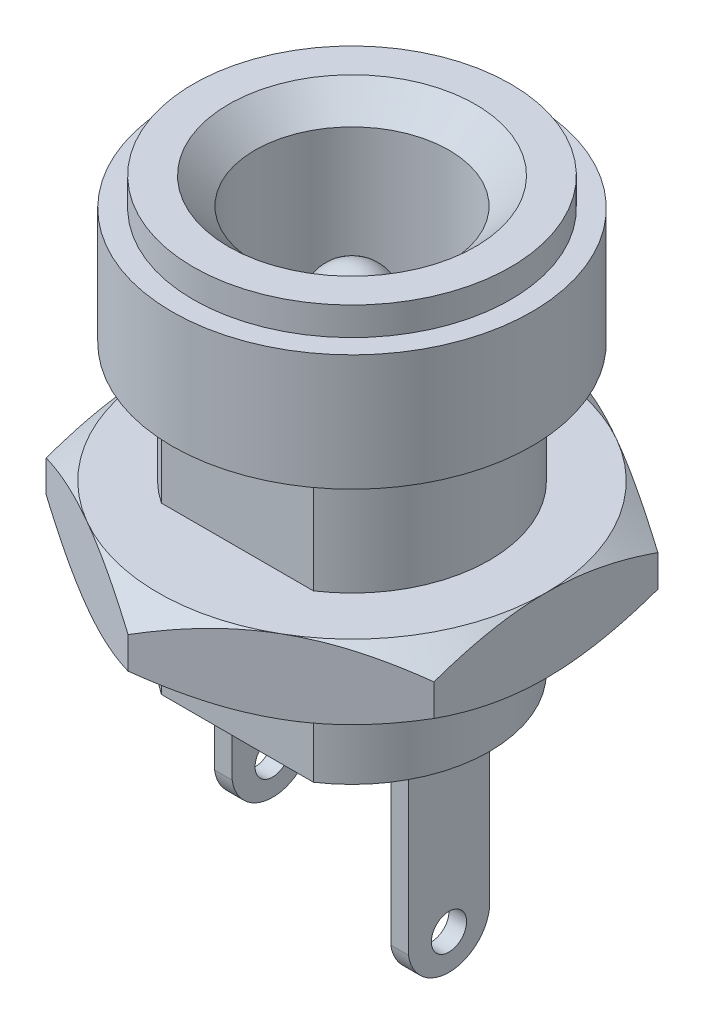
SolidWorks part; units mm, degrees
ref_plane "Front Plane" through (0, 0, 0) normal (0, 0, 1) x (1, 0, 0)
ref_plane "Top Plane" through (0, 0, 0) normal (0, 1, 0) x (1, 0, 0)
ref_plane "Right Plane" through (0, 0, 0) normal (1, 0, 0) x (0, 0, -1)
sketch "Sketch1" plane through (0, 0, 0) normal (0, 0, 1) x (1, 0, 0)
  line L0 (0, 0) -> (0, 12.2) construction
  line L1 (0, 0) -> (3.9, 0) construction
  line L2 (3.9, 0) -> (3.9, 8.1)
  line L3 (3.9, 8.1) -> (5.1, 8.1)
  line L4 (5.1, 8.1) -> (5.1, 11.4)
  line L5 (5.1, 11.4) -> (4.5, 11.4)
  line L6 (4.5, 11.4) -> (4.5, 12.2)
  line L7 (4.5, 12.2) -> (0, 12.2) construction
  line L8 (4.5, 12.2) -> (3.5, 12.2)
  line L9 (3.5, 12.2) -> (2.75, 11.45)
  line L10 (2.75, 11.45) -> (2.75, 3.2)
  line L11 (2.75, 3.2) -> (1.05, 3.2)
  line L12 (1.05, 3.2) -> (1.05, 8.95)
  line L13 (0, 2) -> (1.3, 2)
  line L14 (1.3, 2) -> (1.3, 0)
  line L15 (1.3, 0) -> (3.9, 0)
  line L16 (0, 10) -> (0, 2)
  arc A0 (1.05, 8.95) -> (0, 10) centre (0, 8.95) ccw
  dimension "D1" = 7.8
  dimension "D2" = 12.2
  dimension "D3" = 10.2
  dimension "D4" = 9
  dimension "D5" = 0.8
  dimension "D6" = 4.1
  dimension "D7" = 45
  dimension "D8" = 5.5
  dimension "D9" = 1
  dimension "D10" = 9
  dimension "D11" = 2.1
  dimension "D12" = 2.2
  dimension "D13" = 2.6
  dimension "D14" = 2
revolve "Revolve1" add sketch "Sketch1" angle 360 about L16 other way angle 360
sketch "Sketch2" plane through (0, 0, 0) normal (0, -1, 0) x (1, 0, 0)
  line L0 (2.25, 0) -> (0, 0) construction
  line L1 (2.25, 1.15) -> (2.75, 1.15)
  line L2 (2.25, 1.15) -> (2.25, -1.15)
  line L3 (2.25, -1.15) -> (2.75, -1.15)
  line L4 (2.75, 1.15) -> (2.75, -1.15)
  line L5 (0, 0) -> (-2.25, 0) construction
  line L6 (-2.25, 1.15) -> (-2.75, 1.15)
  line L7 (-2.25, 1.15) -> (-2.25, -1.15)
  line L8 (-2.25, -1.15) -> (-2.75, -1.15)
  line L9 (-2.75, 1.15) -> (-2.75, -1.15)
  dimension "D1" = 2.75
  dimension "D2" = 2.3
  dimension "D3" = 0.5
extrude "Boss-Extrude1" add sketch "Sketch2" along normal blind 6
sketch "Sketch3" plane through (-2.75, 0, 0) normal (-1, 0, 0) x (0, 0, 1)
  line L0 (-1.15, -6) -> (-1.15, 0) construction
  line L1 (1.15, -6) -> (-1.15, -6)
  line L2 (1.15, -6) -> (1.15, -4.2)
  line L3 (1.15, -4.2) -> (-1.15, -4.2)
  line L4 (-1.15, -6) -> (-1.15, -4.2)
  dimension "D1" = 4.2
extrude "Cut-Extrude1" cut sketch "Sketch3" against normal up to next
sketch "Sketch4" plane through (-2.75, 0, 0) normal (-1, 0, 0) x (0, 0, 1)
  line L2 (1.15, -4.2) -> (-1.15, -4.2) construction
  line L3 (1.15, -4.2) -> (1.15, 0) construction
  line L4 (-1.15, -4.2) -> (-1.15, 0) construction
  line L5 (-1.15, -6) -> (-1.15, 0) construction
  line L6 (1.15, -6) -> (1.15, 0) construction
  line L7 (1.15, -6) -> (-1.15, -6) construction
  line L8 (-1.15, -3.2) -> (-1.15, -4.4)
  line L9 (-1.15, -4.4) -> (1.15, -4.4)
  line L10 (1.15, -4.4) -> (1.15, -3.2)
  circle A0 centre (0, -3.2) radius 0.5
  arc A1 (-1.15, -3.2) -> (1.15, -3.2) centre (0, -3.0388) ccw
  circle A2 centre (0, -5) radius 0.5 construction
  arc A3 (-1.15, -5) -> (1.15, -5) centre (0, -4.8387) ccw construction
  dimension "D1" = 1
  dimension "D2" = 3.2
  dimension "D3" = 5
  dimension "D4" = 1.2
extrude "Cut-Extrude2" cut sketch "Sketch4" against normal up to next (0.5 mm away)
sketch "Sketch5" plane through (2.25, 0, 0) normal (-1, 0, 0) x (0, 0, 1)
  line L0 (-1.15, -5) -> (-1.15, -6.5)
  line L1 (-1.15, -6.5) -> (1.15, -6.5)
  line L2 (1.15, -6.5) -> (1.15, -5)
  circle A0 centre (0, -5) radius 0.5 construction
  arc A1 (-1.15, -5) -> (1.15, -5) centre (0, -4.8387) ccw construction
  circle A2 centre (0, -5) radius 0.5
  arc A3 (-1.15, -5) -> (1.15, -5) centre (0, -4.8387) ccw
  dimension "D1" = 1.5
extrude "Cut-Extrude3" cut sketch "Sketch5" against normal up to next (0.5 mm away)
sketch "Sketch6" plane through (0, 0, 0) normal (0, -1, 0) x (1, 0, 0)
  line L0 (0, 3.25) -> (0, -3.25) construction
  line L1 (-5, 3.25) -> (5, 3.25)
  line L2 (-5, 3.25) -> (-5, 13.25)
  line L3 (-5, 13.25) -> (5, 13.25)
  line L4 (5, 3.25) -> (5, 13.25)
  line L5 (5, -3.25) -> (-5, -3.25)
  line L6 (5, -3.25) -> (5, -13.25)
  line L7 (5, -13.25) -> (-5, -13.25)
  line L8 (-5, -3.25) -> (-5, -13.25)
  point P10 (0, 0)
  dimension "D1" = 6.5
  dimension "D2" = 10
extrude "Cut-Extrude4" cut sketch "Sketch6" against normal up to surface (8.1 mm away) up to face at (0, 8.1, 5.1)
ref_plane "Plane1" through (0, 4.7, 0) normal (0, -1, 0) x (-1, 0, 0)
sketch "Sketch7" plane through (0, 4.7, 0) normal (0, -1, 0) x (-1, 0, 0)
  line L1 (0, 6.3509) -> (-5.5, 3.1754)
  line L2 (-5.5, 3.1754) -> (-5.5, -3.1754)
  line L3 (-5.5, -3.1754) -> (0, -6.3509)
  line L4 (0, -6.3509) -> (5.5, -3.1754)
  line L5 (5.5, -3.1754) -> (5.5, 3.1754)
  line L6 (5.5, 3.1754) -> (0, 6.3509)
  circle A0 centre (0, 0) radius 5.5 construction
  dimension "D1" = 11
extrude "Boss-Extrude2" add sketch "Sketch7" along normal blind 2.1
fillet "Fillet1" [suppressed] radius 0.5
sketch "Sketch9" plane through (0, 0, 0) normal (1, 0, 0) x (0, 0, -1)
  line L0 (6.3509, 4.1) -> (5.5, 4.7)
  line L1 (6.3509, 2.6) -> (6.3509, 4.7) construction
  line L2 (6.3509, 4.7) -> (3.1754, 4.7) construction
  line L3 (0, 0) -> (0, 4.7) construction
  line L4 (-3.25, 0) -> (3.25, 0) construction
  line L5 (3.1754, 4.7) -> (-3.1754, 4.7) construction
  line L6 (6.3509, 3.2) -> (5.5, 2.6)
  line L7 (6.3509, 2.6) -> (3.1754, 2.6) construction
  line L8 (6.3509, 4.1) -> (6.3509, 3.2) construction
  line L9 (6.3509, 3.65) -> (0, 3.65) construction
  line L10 (5.5, 4.7) -> (8.5, 4.7)
  line L11 (8.5, 4.7) -> (8.5, 2.6)
  line L12 (8.5, 2.6) -> (5.5, 2.6)
  line L13 (6.3509, 4.1) -> (6.3509, 3.2)
  dimension "D1" = 11
  dimension "D2" = 0.9
  dimension "D3" = 3
revolve "Cut-Revolve1" cut sketch "Sketch9" angle 360 about L3
